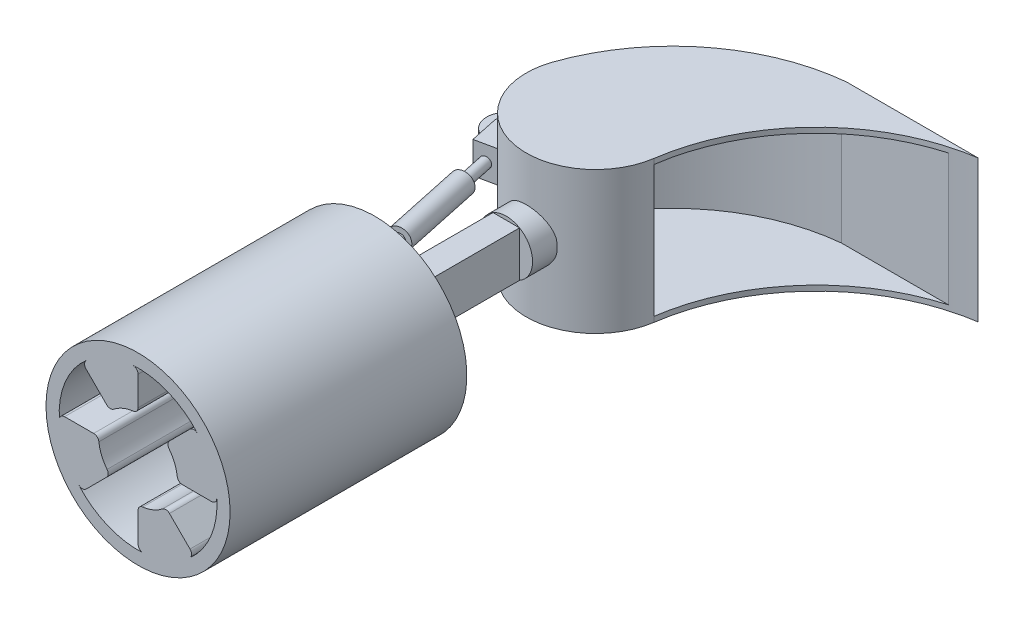
SolidWorks part; units mm, degrees
ref_plane "Front Plane" through (0, 0, 0) normal (0, 0, 1) x (1, 0, 0)
ref_plane "Top Plane" through (0, 0, 0) normal (0, 1, 0) x (1, 0, 0)
ref_plane "Right Plane" through (0, 0, 0) normal (1, 0, 0) x (0, 0, -1)
sketch "Sketch1" plane through (0, 0, 0) normal (0, 1, 0) x (1, 0, 0)
  line L0 (37.4977, 57.9384) -> (87.4977, 57.9384)
  arc A0 (-24.9102, 8.596) -> (26.0797, -3.7755) centre (0, 0) ccw
  arc A1 (37.4977, 57.9384) -> (-24.9102, 8.596) centre (44.8264, -15.4686) ccw
  arc A2 (87.4977, 57.9384) -> (26.0797, -3.7755) centre (98.2999, -14.2307) ccw
  dimension "D1" = 50
extrude "Boss-Extrude1" add sketch "Sketch1" along normal blind 2
sketch "Sketch2" plane through (0, 0, 0) normal (0, -1, 0) x (1, 0, 0)
  line L0 (87.4977, -57.9384) -> (37.4977, -57.9384) construction
  line L1 (87.4977, -57.9384) -> (37.4977, -57.9384)
  line L2 (78.2658, -55.9384) -> (37.598, -55.9384)
  line L3 (24.1004, 3.489) -> (26.0797, 3.7755)
  line L5 (87.4977, -55.9384) -> (37.598, -55.9384) construction
  arc A0 (-24.9102, -8.596) -> (37.4977, -57.9384) centre (44.8264, 15.4686) ccw construction
  arc A2 (26.0797, 3.7755) -> (-24.9102, -8.596) centre (0, 0) ccw construction
  arc A3 (-24.9102, -8.596) -> (37.4977, -57.9384) centre (44.8264, 15.4686) ccw
  arc A5 (26.0797, 3.7755) -> (-24.9102, -8.596) centre (0, 0) ccw
  arc A6 (24.1004, 3.489) -> (-23.0196, -7.9436) centre (0, 0) ccw
  arc A7 (-23.0196, -7.9436) -> (37.598, -55.9384) centre (44.8264, 15.4686) ccw
  arc A8 (26.0797, 3.7755) -> (87.4977, -57.9384) centre (98.2999, 14.2307) ccw construction
  arc A9 (78.2658, -55.9384) -> (87.4977, -57.9384) centre (98.2999, 14.2307) ccw
  dimension "D1" = 2
extrude "Boss-Extrude2" add sketch "Sketch2" along normal blind 50
sketch "Sketch3" plane through (0, -50, 0) normal (0, -1, 0) x (1, 0, 0)
  line L0 (37.4977, -57.9384) -> (87.4977, -57.9384) construction
  line L1 (37.4977, -57.9384) -> (87.4977, -57.9384)
  arc A0 (78.2658, -55.9384) -> (87.4977, -57.9384) centre (98.2999, 14.2307) ccw construction
  arc A1 (26.0797, 3.7755) -> (78.2658, -55.9384) centre (98.2999, 14.2307) ccw construction
  arc A2 (-24.9102, -8.596) -> (37.4977, -57.9384) centre (44.8264, 15.4686) ccw construction
  arc A3 (26.0797, 3.7755) -> (-24.9102, -8.596) centre (0, 0) ccw construction
  arc A4 (78.2658, -55.9384) -> (87.4977, -57.9384) centre (98.2999, 14.2307) ccw
  arc A5 (26.0797, 3.7755) -> (78.2658, -55.9384) centre (98.2999, 14.2307) ccw
  arc A6 (-24.9102, -8.596) -> (37.4977, -57.9384) centre (44.8264, 15.4686) ccw
  arc A7 (26.0797, 3.7755) -> (-24.9102, -8.596) centre (0, 0) ccw
extrude "Boss-Extrude3" add sketch "Sketch3" along normal blind 2
sketch "Sketch4" plane through (0, 0, 0) normal (1, 0, 0) x (0, 0, -1)
  line L0 (-26.3516, 2) -> (-26.3516, -52) construction
  line L1 (-26.3516, -25) -> (-3.7755, -25) construction
  line L2 (-3.7755, -50) -> (-3.7755, 0) construction
  line L3 (-24.5272, -25) -> (-24.5272, -35)
  line L4 (-24.5272, -25) -> (-33.9152, -25)
  line L6 (-24.5272, -35) -> (-33.9152, -35)
  line L7 (-33.9152, -25) -> (-33.9152, -35)
  dimension "D2" = 10
revolve "Revolve1" add sketch "Sketch4" angle 360 about L4
sketch "Sketch5" plane through (0, 0, 33.9152) normal (0, 0, 1) x (1, 0, 0)
  line L1 (-5.0356, -33.6396) -> (5.0356, -33.6396)
  line L2 (-5.0356, -33.6396) -> (-5.0356, -16.3604)
  line L3 (-5.0356, -16.3604) -> (5.0356, -16.3604)
  line L4 (5.0356, -33.6396) -> (5.0356, -16.3604)
  line L5 (-5.0356, -33.6396) -> (5.0356, -16.3604) construction
  line L6 (-5.0356, -16.3604) -> (5.0356, -33.6396) construction
  circle A0 centre (0, -25) radius 10 construction
  point P0 (0, -25)
extrude "Boss-Extrude4" add sketch "Sketch5" along normal blind 50
sketch "Sketch6" plane through (0, 0, 0) normal (0, 0, 1) x (1, 0, 0)
  line L0 (-26.3516, -25) -> (-10, -25) construction
  line L1 (-26.3516, 2) -> (-26.3516, -52) construction
  line L3 (-41.3516, -30) -> (-41.3516, -20)
  line L4 (-41.3516, -20) -> (-26.3516, -20)
  line L5 (-41.3516, -30) -> (-26.3516, -30)
  line L6 (-24.3516, -30) -> (-24.3516, -20)
  line L7 (-26.3516, -20) -> (-24.3516, -20)
  line L8 (-26.3516, -30) -> (-24.3516, -30)
  arc A0 (-5.0356, -16.3604) -> (-5.0356, -33.6396) centre (0, -25) ccw construction
  dimension "D1" = 5
extrude "Boss-Extrude5" add sketch "Sketch6" along normal blind 7.5 and the other way blind 7.5
sketch "Sketch7" plane through (0, -30, 0) normal (0, -1, 0) x (1, 0, 0)
  line L0 (-41.3516, 0) -> (-26.3516, 0) construction
  line L1 (-41.3516, -7.5) -> (-41.3516, 7.5) construction
  line L2 (-33.8516, 7.5) -> (-42.7095, 8.7264)
  line L3 (-42.7095, 8.7264) -> (-44.0538, -0.9827)
  line L4 (-44.0538, -0.9827) -> (-42.2067, -11.5443)
  line L5 (-42.2067, -11.5443) -> (-33.2641, -11.5443)
  line L6 (-33.2641, -11.5443) -> (-33.8516, -7.5)
  arc A0 (26.0797, 3.7755) -> (-24.9102, -8.596) centre (0, 0) ccw construction
  arc A1 (-33.8516, 7.5) -> (-33.8516, -7.5) centre (-33.8516, 0) ccw
extrude "Cut-Extrude1" cut sketch "Sketch7" against normal blind 21.5
sketch "Sketch8" plane through (0, -30, 0) normal (0, -1, 0) x (1, 0, 0)
  arc A0 (-33.8516, 7.5) -> (-33.8516, -7.5) centre (-33.8516, 0) ccw construction
  arc A1 (-33.8516, 7.5) -> (-33.8516, -7.5) centre (-33.8516, 0) ccw
  circle A2 centre (-33.8516, 0) radius 4
extrude "Cut-Extrude2" cut sketch "Sketch8" against normal blind 21.5 contours A2 region at (-33.8516, -30, 0)
sketch "Sketch9" plane through (0, 0, 83.9152) normal (0, 0, 1) x (1, 0, 0)
  line L0 (0, -8.1181) -> (0, 2.9285)
  line L1 (11.9373, -13.0627) -> (19.7484, -5.2516)
  line L2 (16.8819, -25) -> (27.9285, -25)
  line L3 (11.9373, -36.9373) -> (19.7484, -44.7484)
  line L4 (0, -41.8819) -> (0, -52.9285)
  line L5 (-11.9373, -36.9373) -> (-19.7484, -44.7484)
  line L6 (-16.8819, -25) -> (-27.9285, -25)
  line L7 (-11.9373, -13.0627) -> (-19.7484, -5.2516)
  circle A0 centre (0, -25) radius 35
  arc A1 (19.6438, -47.6742) -> (29.9234, -22.8571) centre (0, -25) ccw
  arc A2 (-1.7647, -10.1042) -> (-9.2851, -13.2192) centre (0, -25) ccw
  arc A3 (14.8958, -23.2353) -> (11.7808, -15.7149) centre (0, -25) ccw
  arc A4 (1.7647, -39.8958) -> (9.2851, -36.7808) centre (0, -25) ccw
  arc A5 (-14.8958, -26.7647) -> (-11.7808, -34.2851) centre (0, -25) ccw
  arc A6 (0, -8.1181) -> (-1.7647, -10.1042) centre (-2, -8.1181) cw
  arc A7 (-11.9373, -13.0627) -> (-9.2851, -13.2192) centre (-10.5231, -11.6485) ccw
  arc A8 (-16.8819, -25) -> (-14.8958, -26.7647) centre (-16.8819, -27) cw
  arc A9 (-11.9373, -36.9373) -> (-11.7808, -34.2851) centre (-13.3515, -35.5231) ccw
  arc A10 (0, -41.8819) -> (1.7647, -39.8958) centre (2, -41.8819) cw
  arc A11 (11.9373, -36.9373) -> (9.2851, -36.7808) centre (10.5231, -38.3515) ccw
  arc A12 (16.8819, -25) -> (14.8958, -23.2353) centre (16.8819, -23) cw
  arc A13 (11.9373, -13.0627) -> (11.7808, -15.7149) centre (13.3515, -14.4769) ccw
  arc A14 (19.7484, -5.2516) -> (22.6742, -5.3562) centre (21.1626, -6.6658) cw
  arc A15 (27.9285, -25) -> (29.9234, -22.8571) centre (27.9285, -23) ccw
  arc A16 (19.7484, -44.7484) -> (19.6438, -47.6742) centre (18.3342, -46.1626) cw
  arc A17 (0, -52.9285) -> (2.1429, -54.9234) centre (2, -52.9285) ccw
  arc A18 (-19.7484, -44.7484) -> (-22.6742, -44.6438) centre (-21.1626, -43.3342) cw
  arc A19 (-27.9285, -25) -> (-29.9234, -27.1429) centre (-27.9285, -27) ccw
  arc A20 (-19.7484, -5.2516) -> (-19.6438, -2.3258) centre (-18.3342, -3.8374) cw
  arc A21 (0, 2.9285) -> (-2.1429, 4.9234) centre (-2, 2.9285) ccw
  arc A22 (-19.6438, -2.3258) -> (-29.9234, -27.1429) centre (0, -25) ccw
  arc A23 (22.6742, -5.3562) -> (-2.1429, 4.9234) centre (0, -25) ccw
  arc A24 (-22.6742, -44.6438) -> (2.1429, -54.9234) centre (0, -25) ccw
  point P24 (0, -25)
  point P53 (0, 5)
  dimension "D1" = 70
  dimension "D2" = 2
extrude "Boss-Extrude7" add sketch "Sketch9" along normal blind 90 separate body
sketch "Sketch12" plane through (0, 0, 83.9152) normal (0, 0, -1) x (-1, 0, 0)
  circle A0 centre (0, -25) radius 35
extrude "Boss-Extrude8" add sketch "Sketch12" against normal blind 10
ref_plane "Plane1" through (0, -25, 0) normal (0, -1, 0) x (-1, 0, 0)
sketch "Sketch13" plane through (0, -25, 0) normal (0, -1, 0) x (-1, 0, 0)
  line L0 (5.0356, -83.9152) -> (5.0356, -33.9152) construction
  line L1 (5.0356, -68.9152) -> (17.5356, -68.9152)
  line L2 (5.0356, -68.9152) -> (5.0356, -83.9152)
  line L3 (5.0356, -83.9152) -> (17.5356, -83.9152)
  line L6 (5.0356, -76.4152) -> (25.0356, -76.4152) construction
  arc A1 (17.5356, -83.9152) -> (17.5356, -68.9152) centre (17.5356, -76.4152) ccw
  circle A3 centre (17.5356, -76.4152) radius 4
extrude "Boss-Extrude9" add sketch "Sketch13" along normal blind 5 and the other way blind 5
sketch "Sketch14" plane through (0, -20, 0) normal (0, 1, 0) x (1, 0, 0)
  line L0 (-37.7634, -0.8352) -> (-21.4475, -77.2504)
  line L1 (-29.9398, 0.8352) -> (-13.6238, -75.5799)
  arc A0 (-29.9398, 0.8352) -> (-37.7634, -0.8352) centre (-33.8516, 0) ccw
  arc A1 (-21.4475, -77.2504) -> (-13.6238, -75.5799) centre (-17.5356, -76.4152) ccw
extrude "Boss-Extrude10" add sketch "Sketch14" against normal blind 11 and the other way blind 1
sketch "Sketch15" plane through (0, -25, 0) normal (0, -1, 0) x (-1, 0, 0)
  line L2 (33.6379, -10.5788) -> (35.5938, -10.9964)
  line L5 (37.7634, -0.8352) -> (21.4475, -77.2504) construction
  line L6 (35.5938, -10.9964) -> (37.8093, -11.4694)
  line L7 (31.682, -10.1612) -> (19.6591, -66.4701) construction
  line L8 (33.6379, -10.5788) -> (31.2808, -21.6184)
  line L12 (33.0908, -13.1415) -> (31.2808, -21.6184)
  line L13 (31.2808, -21.6184) -> (33.2367, -22.0361)
  line L14 (24.7533, -52.1897) -> (26.7092, -52.6073)
  line L15 (33.2367, -22.0361) -> (26.7092, -52.6073)
  line L16 (24.7533, -52.1897) -> (21.615, -66.8877)
  line L17 (24.7533, -52.1897) -> (22.2538, -63.8961)
  line L18 (33.6379, -10.5788) -> (21.615, -66.8877) construction
  line L20 (24.0425, -67.406) -> (25.7863, -67.7784)
  line L21 (21.615, -66.8877) -> (24.0425, -67.406)
  line L22 (38.7872, -11.6783) -> (26.7643, -67.9872)
  line L23 (37.8093, -11.4694) -> (38.7872, -11.6783)
  line L24 (25.7863, -67.7784) -> (26.7643, -67.9872)
  dimension "D1" = 2
revolve "Cut-Revolve3" cut sketch "Sketch15" angle 360 about L7 region at (-30.5145, -25, 39.8468)
